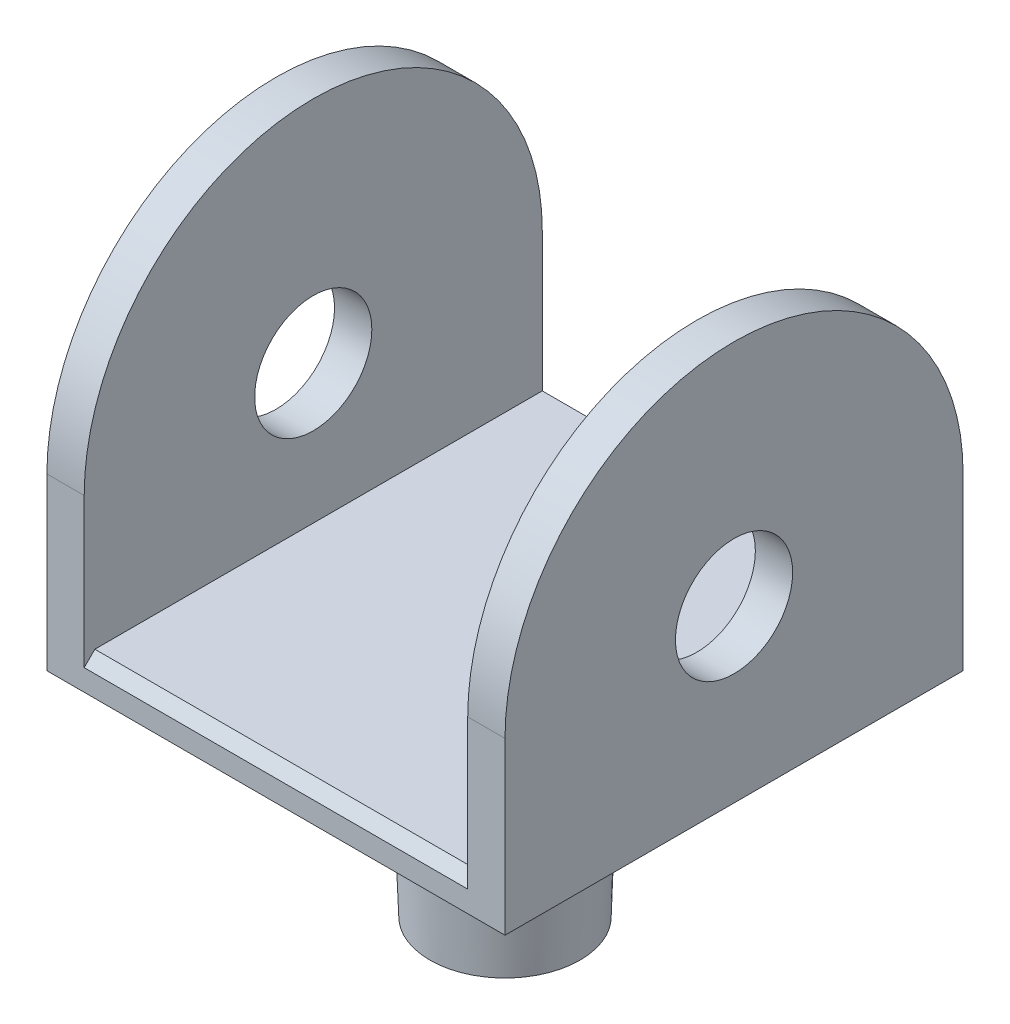
SolidWorks part; units mm, degrees
material "Plywood"
ref_plane "Front Plane" through (0, 0, 0) normal (0, 0, 1) x (1, 0, 0)
ref_plane "Top Plane" through (0, 0, 0) normal (0, 1, 0) x (1, 0, 0)
ref_plane "Right Plane" through (0, 0, 0) normal (1, 0, 0) x (0, 0, -1)
sketch "Sketch2" plane through (0, 0, 0) normal (0, 0, 1) x (1, 0, 0)
  line L0 (0, 0) -> (15.5, 0)
  line L1 (15.5, 0) -> (14.1032, -40)
  line L2 (14.1032, -40) -> (0, -40)
  line L3 (0, -40) -> (0, 0)
  line L4 (0, -16.8839) -> (0, 47607.9041) construction
  point P15 (0, -20)
  dimension "D1" = 31
  dimension "D2" = 2
  dimension "D3" = 40
  dimension "D4" = 28.2063
revolve "Revolve1" add sketch "Sketch2" angle 360 about L4
sketch "Sketch3" plane through (0, 0, 0) normal (0, 1, 0) x (1, 0, 0)
  line L1 (-43, -43) -> (43, -43)
  line L2 (-43, -43) -> (-43, 43)
  line L3 (-43, 43) -> (43, 43)
  line L4 (43, -43) -> (43, 43)
  line L5 (-43, -43) -> (43, 43) construction
  line L6 (-43, 43) -> (43, -43) construction
  point P0 (0, 0)
  dimension "D1" = 86
extrude "Boss-Extrude1" add sketch "Sketch3" along normal blind 6
fillet "Fillet2" radius 2 1 edges at (0, 0, -15.5)
sketch "Sketch4" plane through (0, 0, 0) normal (1, 0, 0) x (0, 0, -1)
  line L0 (-43, 6) -> (43, 6) construction
  line L1 (-43, 6) -> (43, 6)
  line L2 (-43, 6) -> (-43, 32)
  line L4 (43, 32) -> (43, 6)
  arc A0 (-43, 32) -> (43, 32) centre (0, 32) cw
  circle A1 centre (0, 32) radius 11
  dimension "D2" = 22
  dimension "D1" = 26
extrude "Boss-Extrude2" add sketch "Sketch4" against normal up to surface (43 mm away) from surface up to face at (-43, 3, 0) starting at face at (43, 3, 0)
extrude "Cut-Extrude1" cut sketch "Sketch4<2>" against normal mid plane 72
sketch "Sketch4<2>" plane through (0, 0, 0) normal (1, 0, 0) x (0, 0, -1) same geometry as "Sketch4"
chamfer "Chamfer2" distance 2 angle 45 1 edges at (0, 6, 43)
